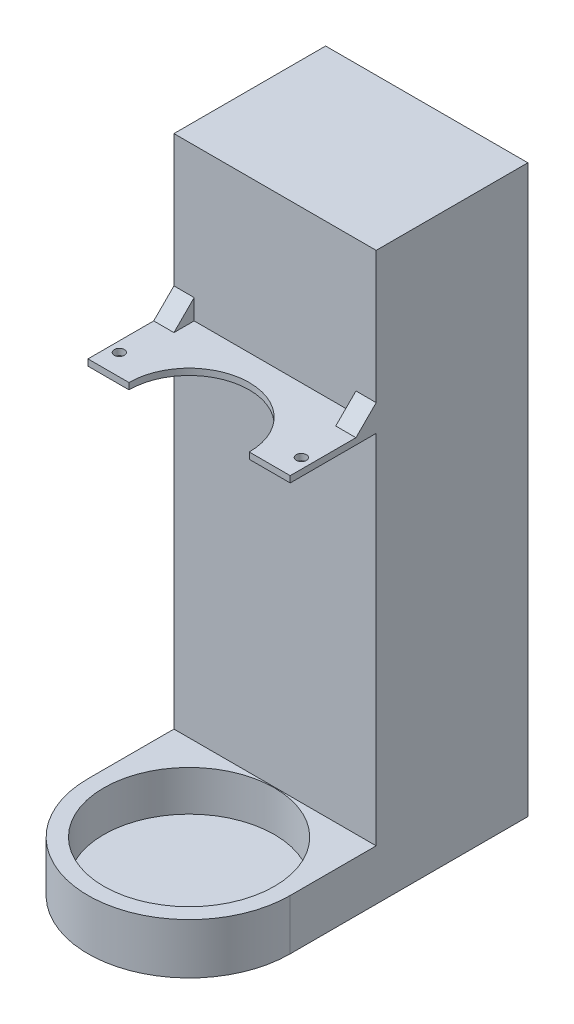
SolidWorks part; units mm, degrees
ref_plane "Front Plane" through (0, 0, 0) normal (0, 0, 1) x (1, 0, 0)
ref_plane "Top Plane" through (0, 0, 0) normal (0, 1, 0) x (1, 0, 0)
ref_plane "Right Plane" through (0, 0, 0) normal (1, 0, 0) x (0, 0, -1)
sketch "Sketch1" plane through (0, 0, 0) normal (0, 0, 1) x (1, 0, 0)
  line L1 (-25.4, -71.12) -> (25.4, -71.12)
  line L2 (-25.4, -71.12) -> (-25.4, 71.12)
  line L3 (-25.4, 71.12) -> (25.4, 71.12)
  line L4 (25.4, -71.12) -> (25.4, 71.12)
  line L5 (-25.4, -71.12) -> (25.4, 71.12) construction
  line L6 (-25.4, 71.12) -> (25.4, -71.12) construction
  point P0 (0, 0)
  dimension "D1" = 142.24
  dimension "D2" = 50.8
extrude "Boss-Extrude1" add sketch "Sketch1" along normal blind 38.1
sketch "Sketch8" plane through (0, -71.12, 0) normal (0, -1, 0) x (1, 0, 0)
  line L1 (-25.4, 38.1) -> (-25.4, 59.69)
  line L2 (25.4, 38.1) -> (25.4, 59.69)
  line L3 (-25.4, 38.1) -> (25.4, 38.1) construction
  line L4 (-25.4, 38.1) -> (25.4, 38.1)
  arc A0 (25.4, 59.69) -> (-25.4, 59.69) centre (0, 59.69) ccw
  circle A1 centre (0, 59.69) radius 21.4313
  dimension "D2" = 21.59
  dimension "D1" = 25.4
  dimension "D3" = 42.8625
extrude "Boss-Extrude2" add sketch "Sketch8" against normal blind 2.54 separate body contours L4 A1 L2 A0 L1 | A1 region at (-24.708, -71.12, 48.895) region at (0, -71.12, 59.69)
extrude "Boss-Extrude9" add sketch "Sketch8<5>" against normal blind 12.7 contours L2 A0 L1 L4 A1 region at (-24.708, -71.12, 48.895)
sketch "Sketch8<5>" plane through (0, -71.12, 0) normal (0, -1, 0) x (1, 0, 0) same geometry as "Sketch8"
sketch "Sketch18" plane through (0, 0, 38.1) normal (0, 0, 1) x (1, 0, 0)
  line L0 (0, -58.42) -> (0, 32.1084) construction
  line L1 (25.4, -58.42) -> (-25.4, -58.42) construction
  point P7 (0, 0)
ref_plane "Plane1" through (0, 32.1084, 0) normal (0, 1, 0) x (1, 0, 0)
sketch "Sketch15" plane through (0, 32.1084, 0) normal (0, 1, 0) x (1, 0, 0)
  line L0 (-15.113, -59.69) -> (-25.4, -59.69)
  line L1 (-25.4, -59.69) -> (-25.4, -38.1)
  line L2 (-25.4, -38.1) -> (25.4, -38.1)
  line L3 (25.4, -38.1) -> (25.4, -59.69)
  line L4 (25.4, -59.69) -> (15.113, -59.69)
  arc A2 (15.113, -59.69) -> (-15.113, -59.69) centre (0, -59.69) ccw
  arc A3 (-25.4, -59.69) -> (25.4, -59.69) centre (0, -59.69) ccw construction
  point P4 (0, -59.69)
  dimension "D1" = 15.113
extrude "Boss-Extrude13" add sketch "Sketch15" along normal mid plane 1.5971
sketch "Sketch16" plane through (0, 32.9069, 0) normal (0, 1, 0) x (1, 0, 0)
  line L0 (-25.4, -59.69) -> (-15.113, -59.69) construction
  line L1 (-25.4, -38.1) -> (-25.4, -59.69) construction
  circle A0 centre (-22.86, -54.356) radius 1.27
  dimension "D1" = 2.54
  dimension "D2" = 5.334
  dimension "D3" = 2.54
extrude "Cut-Extrude7" cut sketch "Sketch16" against normal up to surface (1.5971 mm away) up to face at (0, 31.3098, 49.9745)
mirror "Mirror1" about plane through (0, 0, 0) normal (1, 0, 0) of "Cut-Extrude7"
sketch "Sketch17" plane through (25.4, 0, 0) normal (1, 0, 0) x (0, 0, -1)
  line L0 (-38.1, 32.9069) -> (-38.1, 37.9869)
  line L1 (-38.1, 32.9069) -> (-38.1, 71.12) construction
  line L2 (-38.1, 37.9869) -> (-43.18, 32.9069)
  line L3 (-59.69, 32.9069) -> (-38.1, 32.9069) construction
  line L4 (-43.18, 32.9069) -> (-38.1, 32.9069)
  dimension "D1" = 5.08
extrude "Boss-Extrude14" add sketch "Sketch17" against normal blind 5.08
mirror "Mirror2" about plane through (0, 0, 0) normal (1, 0, 0) of "Boss-Extrude14"
